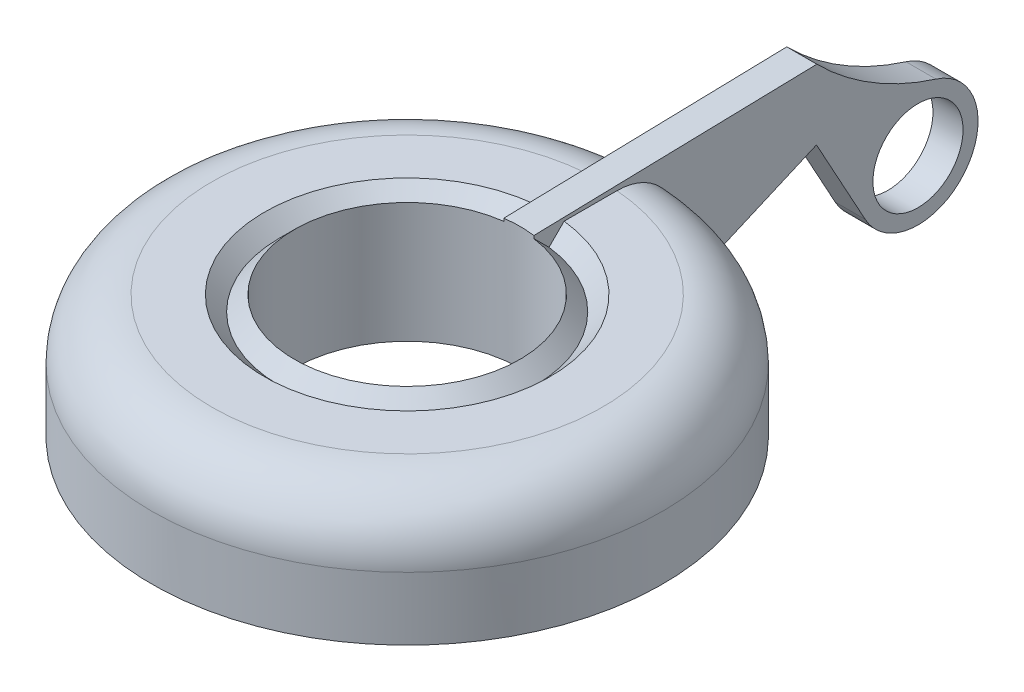
SolidWorks part; units mm, degrees
ref_plane "Front Plane" through (0, 0, 0) normal (0, 0, 1) x (1, 0, 0)
ref_plane "Top Plane" through (0, 0, 0) normal (0, 1, 0) x (1, 0, 0)
ref_plane "Right Plane" through (0, 0, 0) normal (1, 0, 0) x (0, 0, -1)
sketch "Sketch4" plane through (0, 0, 0) normal (1, 0, 0) x (0, 0, -1)
  line L0 (0, 0) -> (-3.75, 0)
  line L1 (-3.75, 0) -> (-4.25, -0.5)
  line L2 (-4.25, -0.5) -> (-4.75, 0)
  line L3 (-4.75, 0) -> (-8.5, 0)
  line L4 (-8.5, 0) -> (-8.5, -4)
  line L5 (-8.5, -4) -> (0, -4)
  line L6 (0, 0) -> (0, -4)
  line L7 (-8.5, -0.5) -> (0, -0.5) construction
  line L8 (0, 1.8905) -> (0, -6.6755) construction
  point P3 (-4.25, -0.5)
  dimension "D1" = 8.5
  dimension "D2" = 0.5
  dimension "D3" = 4
revolve "Revolve1" add sketch "Sketch4" angle 360 about L8
fillet "Fillet1" radius 2 1 edges at (0, 0, 8.5)
sketch "Sketch5" plane through (0, -4, 0) normal (0, -1, 0) x (1, 0, 0)
  circle A0 centre (0, 0) radius 8.5
  circle A1 centre (0, 0) radius 7
  dimension "D1" = 14
extrude "Boss-Extrude1" add sketch "Sketch5" along normal blind 0.1 separate body
sketch "Sketch6" plane through (0, 0, 0) normal (1, 0, 0) x (0, 0, -1)
  line L0 (0, 0) -> (13.1329, 0.32)
  line L1 (8.5, -4) -> (13.1218, -1.9998)
  line L2 (8.5, -4) -> (8.5, -2) construction
  line L3 (8.5, -4) -> (-8.5, -4) construction
  line L4 (13.1218, -1.9998) -> (14.7464, -4.9618)
  line L5 (0, 0) -> (0, -0.9077)
  line L6 (0, -0.9077) -> (7.1744, -0.9077)
  line L7 (7.1744, -0.9077) -> (8.5, -4)
  circle A0 centre (16.5, -4) radius 1.5
  circle A1 centre (16.5, -4) radius 2
  arc A2 (13.1329, 0.32) -> (17.0986, -2.0917) centre (19.992, 7.1325) ccw
  dimension "D1" = 3
  dimension "D2" = 4
  dimension "D3" = 16.5
extrude "Boss-Extrude2" add sketch "Sketch6" along normal blind 0.5 and the other way blind 0.5 contours A2 L0 L5 L6 L7 L1 L4 A1 | A1 A0 region at (0, -1.2698, -9.4758) region at (0, -2.8497, -18.0664)
sketch "Sketch7" plane through (0, 0, 0) normal (0, 1, 0) x (1, 0, 0)
  circle A0 centre (0, 0) radius 3.75
  dimension "D1" = 7.5
extrude "Cut-Extrude1" cut sketch "Sketch7" against normal through all both and the other way through all
